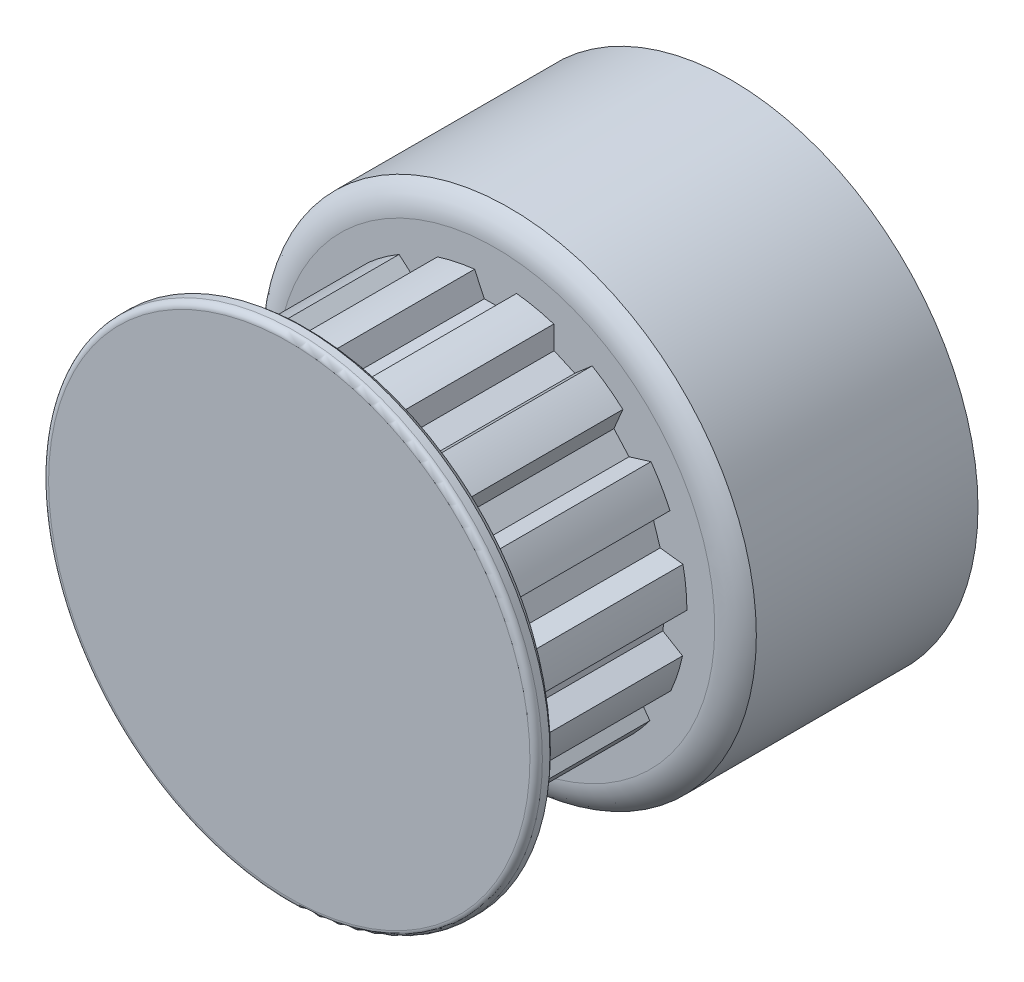
SolidWorks part; units mm, degrees
ref_plane "Front Plane" through (0, 0, 0) normal (0, 0, 1) x (1, 0, 0)
ref_plane "Top Plane" through (0, 0, 0) normal (0, 1, 0) x (1, 0, 0)
ref_plane "Right Plane" through (0, 0, 0) normal (1, 0, 0) x (0, 0, -1)
sketch "Sketch1" plane through (0, 0, 0) normal (0, 0, 1) x (1, 0, 0)
  line L0 (-1.2827, 11.6205) -> (-0.6905, 10.3505)
  line L1 (-0.6905, 10.3505) -> (0.6905, 10.3505)
  line L2 (0.6905, 10.3505) -> (1.2827, 11.6205)
  line L3 (-1.2827, 11.6205) -> (1.2827, 11.6205)
  line L4 (0, 0) -> (0, 10.3505) construction
  line L5 (0, 10.3505) -> (0, 12.6365) construction
  circle A0 centre (0, 0) radius 12.1285 construction
  circle A1 centre (0, 0) radius 15.0876 construction
  circle A2 centre (0, 0) radius 11.6911 construction
  point P6 (0, 11.6205)
  point P11 (0, 12.1285)
  point P13 (0, 15.0876)
  point P14 (0, 11.6911)
  dimension "D1" = 1.016
  dimension "PD" = 24.257
  dimension "D2" = 0.508
  dimension "OD" = 30.1752
  dimension "b" = 50
  dimension "bt" = 2.5654
  dimension "ht" = 1.27
  dimension "hs" = 2.286
sketch "Sketch2" plane through (0, 0, 0) normal (1, 0, 0) x (0, 0, -1)
  line L0 (-11.8745, 0) -> (11.8745, 0)
  line L1 (-11.8745, 0) -> (-11.8745, 7.9375)
  line L2 (-11.8745, 7.9375) -> (-2.4257, 7.9375)
  line L3 (-2.4257, 7.9375) -> (-2.4257, 15.0876)
  line L4 (-2.4257, 15.0876) -> (-0.7366, 15.0876) construction
  line L5 (-0.7366, 15.0876) -> (-0.7366, 11.6911) construction
  line L6 (-0.7366, 11.6911) -> (10.1854, 11.6911)
  line L7 (10.1854, 11.6911) -> (10.1854, 15.0876) construction
  line L8 (10.1854, 15.0876) -> (11.8745, 15.0876) construction
  line L9 (11.8745, 15.0876) -> (11.8745, 0)
  line L10 (-11.8745, 0) -> (11.8745, 0) construction
  line L13 (-2.4257, 15.0876) -> (-1.5811, 15.0876)
  line L14 (-0.7366, 13.3893) -> (-0.7366, 11.6911)
  line L15 (10.1854, 11.6911) -> (10.1854, 13.3893)
  line L16 (11.0299, 15.0876) -> (11.8745, 15.0876)
  arc A0 (-0.7366, 13.3893) -> (-1.5811, 15.0876) centre (-2.8663, 13.3893) ccw
  arc A1 (10.1854, 13.3893) -> (11.0299, 15.0876) centre (12.3151, 13.3893) cw
  point P12 (-0.7366, 13.3893)
  point P14 (-1.5811, 15.0876)
  point P20 (10.1854, 13.3893)
  point P21 (11.0299, 15.0876)
  point P25 (10.1854, 0)
  point P26 (-0.7366, 0)
  dimension "OA" = 23.749
  dimension "Hub Dia" = 15.875
  dimension "Outside Width" = 14.3002
  dimension "Inside Width" = 10.922
revolve "Revolve1" add sketch "Sketch2" angle 360 mid plane about L10
sketch "Sketch3" plane through (0, 0, 0) normal (0, 0, 1) x (1, 0, 0)
  line L0 (-0.6905, 10.3505) -> (0.6905, 10.3505) construction
  line L1 (0.6905, 10.3505) -> (1.2827, 11.6205) construction
  line L2 (-1.2827, 11.6205) -> (-0.6905, 10.3505) construction
  line L3 (-0.6905, 10.3505) -> (0.6905, 10.3505)
  line L4 (0.6905, 10.3505) -> (1.2827, 11.6205)
  line L5 (-1.2827, 11.6205) -> (-0.6905, 10.3505)
  circle A0 centre (0, 0) radius 11.6911 construction
  arc A1 (1.2827, 11.6205) -> (-1.2827, 11.6205) centre (0, 0) ccw
extrude "Cut-Extrude1" cut sketch "Sketch3" against normal up to vertex (10.1854 mm away) from vertex up to point (0, 11.6911, -10.1854) starting at point (0, 11.6911, 0.7366)
pattern_circular "CirPattern1" count 15 over 360 about axis through (0, 0, 0.7366) along (0, 0, 1) of "Cut-Extrude1"
split "Split1" bodies to split 103 resulting bodies 108 109 split by face at (7.9375, 0, 2.4257)
delete or keep bodies "Body-Delete/Keep 1" type delete bodies bodies 109
fillet "Fillet1" radius 0.381 1 edges at (15.0876, 0, 2.4257)
ref_plane "Plane1" through (0, 0, -11.8745) normal (0, 0, -1) x (-1, 0, 0)
sketch "Sketch6" plane through (0, 0, -11.8745) normal (0, 0, -1) x (-1, 0, 0)
  line L0 (0, 13.8564) -> (0, -13.8564) construction
  line L1 (-12, 6.9282) -> (-12, -6.9282)
  line L2 (-12, -6.9282) -> (0, -13.8564)
  line L3 (0, -13.8564) -> (12, -6.9282)
  line L4 (12, -6.9282) -> (12, 6.9282)
  line L5 (12, 6.9282) -> (0, 13.8564)
  line L6 (0, 13.8564) -> (-12, 6.9282)
  line L7 (-12, 6.9282) -> (12, -6.9282) construction
  line L8 (12, 6.9282) -> (-12, -6.9282) construction
  point P0 (0, 0)
  point P7 (-12, 6.9282)
  point P8 (12, 6.9282)
  dimension "D1" = 13.8564
  dimension "D2" = 120
sketch "Sketch7" plane through (0, 0, -11.8745) normal (0, 0, -1) x (-1, 0, 0)
  circle A0 centre (0, 0) radius 15.0876
extrude "Boss-Extrude1" add sketch "Sketch7" along normal blind 12.7
extrude "Cut-Extrude3" cut sketch "Sketch6" along normal up to surface (12.7 mm away) up to face at (-15.0876, 0, -24.5745)
